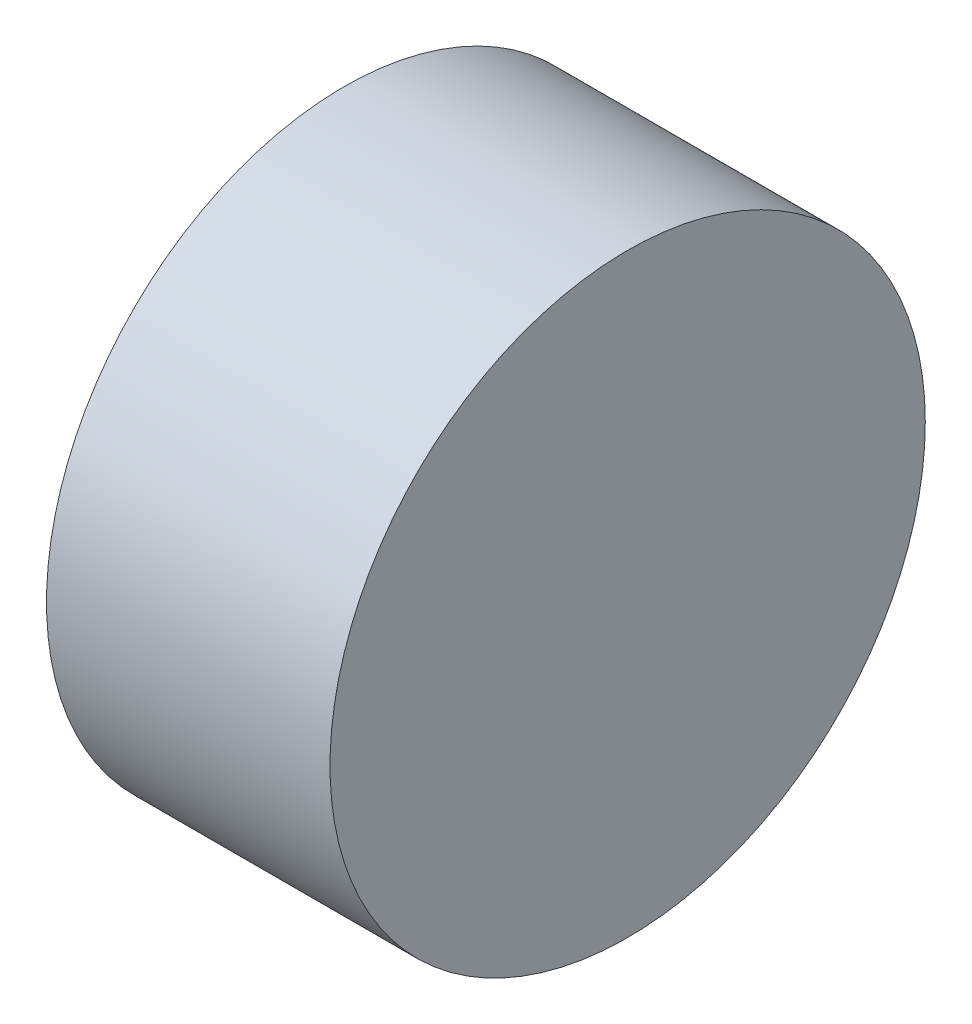
SolidWorks part; units mm, degrees
ref_plane "Front Plane" through (0, 0, 0) normal (0, 0, 1) x (1, 0, 0)
ref_plane "Top Plane" through (0, 0, 0) normal (0, 1, 0) x (1, 0, 0)
ref_plane "Right Plane" through (0, 0, 0) normal (1, 0, 0) x (0, 0, -1)
sketch "Sketch1" plane through (0, 0, 0) normal (1, 0, 0) x (0, 0, -1)
  circle A0 centre (0, 0) radius 64.8
extrude "Boss-Extrude1" add sketch "Sketch1" along normal blind 61.72
ref_axis "WheelAxis" through (0, 0, 0) along (1, 0, 0)
